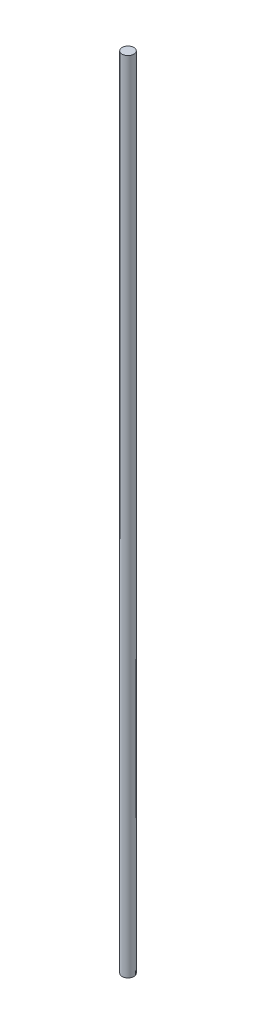
SolidWorks part; units mm, degrees
material "AISI 1020"
ref_plane "Front Plane" through (0, 0, 0) normal (0, 0, 1) x (1, 0, 0)
ref_plane "Top Plane" through (0, 0, 0) normal (0, 1, 0) x (1, 0, 0)
ref_plane "Right Plane" through (0, 0, 0) normal (1, 0, 0) x (0, 0, -1)
sketch "Sketch1" plane through (0, 0, 0) normal (0, 1, 0) x (1, 0, 0)
  circle A0 centre (0, 0) radius 2.5
  dimension "D1" = 5
extrude "Boss-Extrude1" add sketch "Sketch1" along normal blind 170 and the other way blind 170
cosmetic thread "Cosmetic Thread1" parameters "D2"=4
